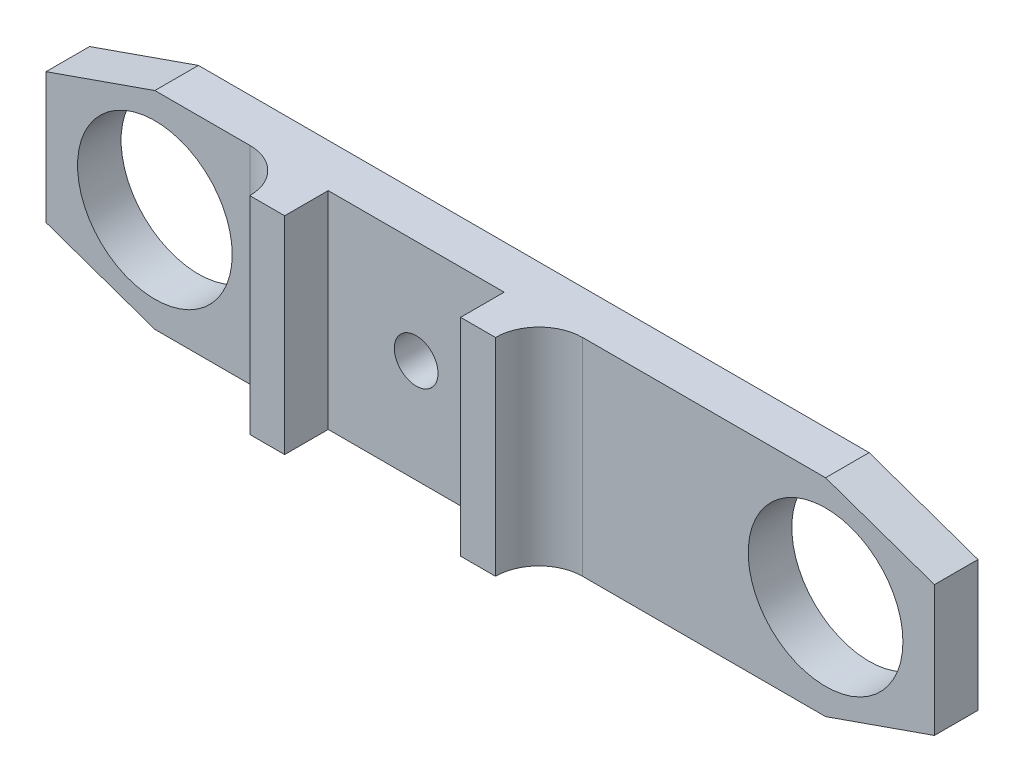
SolidWorks part; units mm, degrees
ref_plane "Front Plane" through (0, 0, 0) normal (0, 0, 1) x (1, 0, 0)
ref_plane "Top Plane" through (0, 0, 0) normal (0, 1, 0) x (1, 0, 0)
ref_plane "Right Plane" through (0, 0, 0) normal (1, 0, 0) x (0, 0, -1)
sketch "Sketch1" plane through (0, 0, 0) normal (0, 0, 1) x (1, 0, 0)
  line L0 (0, 0) -> (31215.3166, 0) construction
  line L1 (-38.1, 15.0812) -> (59.69, 15.0813)
  line L2 (59.69, 15.0813) -> (75.565, 9.525)
  line L3 (75.565, 9.525) -> (75.565, -9.525)
  line L4 (75.565, -9.525) -> (59.69, -15.0813)
  line L5 (59.69, -15.0813) -> (-38.1, -15.0813)
  line L6 (-38.1, -15.0813) -> (-53.975, -9.525)
  line L7 (-53.975, -9.525) -> (-53.975, 9.525)
  line L8 (-53.975, 9.525) -> (-38.1, 15.0812)
  circle A0 centre (0, 0) radius 3.1877
  circle A1 centre (-38.1, 0) radius 11.2776
  circle A2 centre (59.69, 0) radius 11.2776
  point P17 (-53.975, 0)
  point P18 (75.565, 0)
  dimension "D3" = 22.5552
  dimension "D5" = 6.3754
  dimension "D1" = 38.1
  dimension "D2" = 59.69
  dimension "D4" = 15.875
  dimension "D6" = 19.05
  dimension "D7" = 30.1625
extrude "Boss-Extrude1" add sketch "Sketch1" along normal blind 6.35
sketch "Sketch2" plane through (0, 0, 6.35) normal (0, 0, 1) x (1, 0, 0)
  line L0 (59.69, 15.0813) -> (-38.1, 15.0812) construction
  line L1 (-12.827, -15.0813) -> (12.827, -15.0813)
  line L2 (-12.827, -15.0813) -> (-12.827, 15.0813)
  line L3 (-12.827, 15.0813) -> (12.827, 15.0813)
  line L4 (12.827, -15.0813) -> (12.827, 15.0813)
  line L5 (-12.827, -15.0813) -> (12.827, 15.0813) construction
  line L6 (-12.827, 15.0813) -> (12.827, -15.0813) construction
  line L8 (-17.907, -15.0813) -> (17.907, -15.0813)
  line L9 (-17.907, -15.0813) -> (-17.907, 15.0813)
  line L10 (-17.907, 15.0813) -> (17.907, 15.0813)
  line L11 (17.907, -15.0813) -> (17.907, 15.0813)
  line L12 (-17.907, -15.0813) -> (17.907, 15.0813) construction
  line L13 (-17.907, 15.0813) -> (17.907, -15.0813) construction
  point P0 (0, 0)
  point P8 (0, 0)
  line M5 (-38.1, -15.0813) -> (59.69, -15.0813)
  line M9 (59.69, 15.0813) -> (-38.1, 15.0812)
  dimension "D1" = 25.654
  dimension "D2" = 5.08
extrude "Boss-Extrude2" add sketch "Sketch2" along normal blind 6.35 contours L9 L2 M5 M9 | L11 L4 M5 M9 region at (-15.367, 0, 6.35) region at (15.367, 0, 6.35)
fillet "Fillet1" radius 6.35 2 edges at (-17.907, 0, 6.35) (17.907, 0, 6.35)
